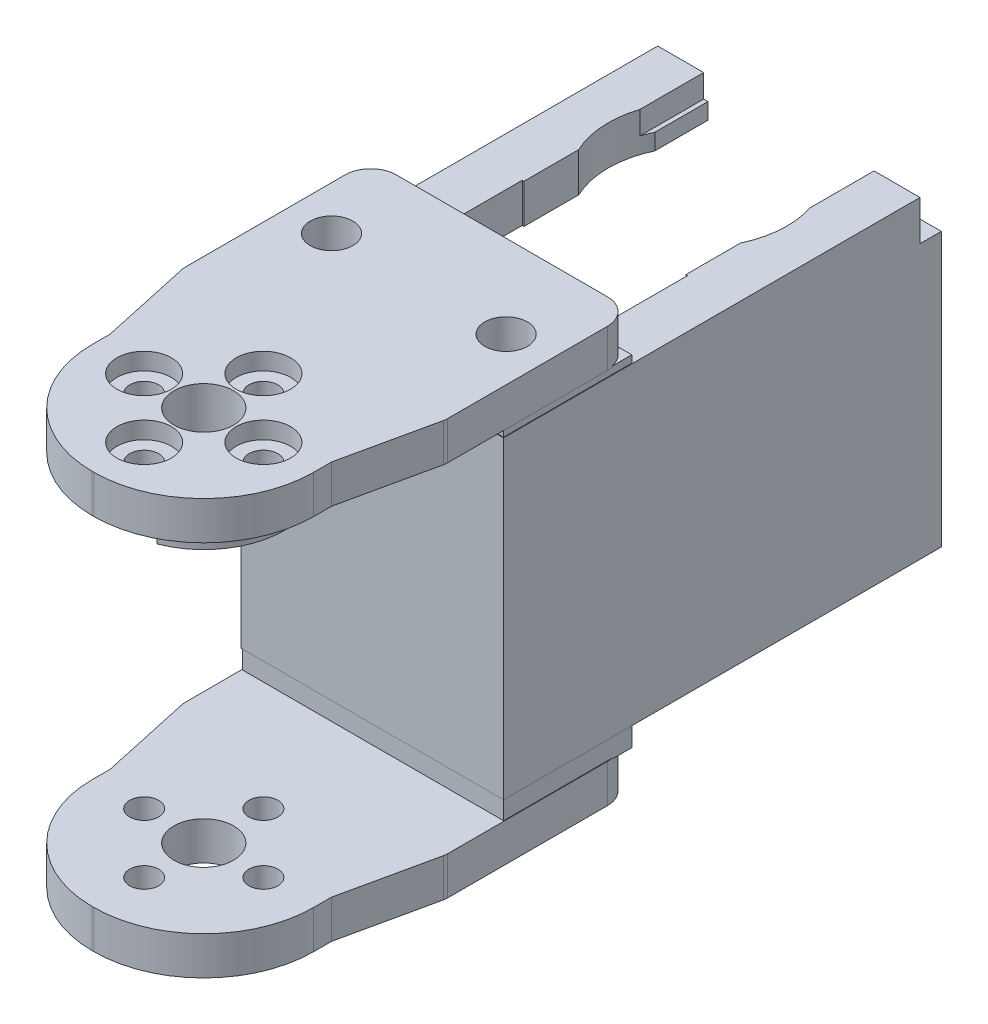
SolidWorks part; units mm, degrees
ref_plane "Front Plane" through (0, 0, 0) normal (0, 0, 1) x (1, 0, 0)
ref_plane "Top Plane" through (0, 0, 0) normal (0, 1, 0) x (1, 0, 0)
ref_plane "Right Plane" through (0, 0, 0) normal (1, 0, 0) x (0, 0, -1)
ref_plane "PY_m23_300" through (0, -23.3, 0) normal (0, 1, 0) x (1, 0, 0)
sketch "S_prism1" plane through (0, -23.3, 0) normal (0, 1, 0) x (1, 0, 0)
  line L0 (-13, 2) -> (-15.354, 12.7893)
  line L1 (-15.4, 13.2156) -> (-15.4, 32)
  line L2 (-12.4, 35) -> (12.4, 35)
  line L3 (15.4, 32) -> (15.4, 13.2156)
  line L4 (15.354, 12.7893) -> (13, 2)
  line L5 (13, 2) -> (13, -0.1)
  line L6 (0.1, -13) -> (-0.1, -13)
  line L7 (-13, -0.1) -> (-13, 2)
  arc A0 (-15.354, 12.7893) -> (-15.4, 13.2156) centre (-13.4076, 13.215) cw
  arc A1 (-15.4, 32) -> (-12.4, 35) centre (-12.3999, 31.9999) cw
  arc A2 (12.4, 35) -> (15.4, 32) centre (12.3999, 31.9999) cw
  arc A3 (15.4, 13.2156) -> (15.354, 12.7893) centre (13.4076, 13.215) cw
  arc A4 (13, -0.1) -> (0.1, -13) centre (0.1001, -0.1001) cw
  arc A5 (-0.1, -13) -> (-13, -0.1) centre (-0.1001, -0.1001) cw
extrude "Boss_1" add sketch "S_prism1" along normal blind 4.5
ref_plane "PY_p17_750" through (0, 17.75, 0) normal (0, 1, 0) x (1, 0, 0)
sketch "S_cyl2" plane through (0, 17.75, 0) normal (0, 1, 0) x (1, 0, 0)
  circle A0 centre (0, 0) radius 9.5
  dimension "D1_S_cyl2" = 19
extrude "Boss_2" add sketch "S_cyl2" along normal blind 3.2
ref_plane "PY_p20_950" through (0, 20.95, 0) normal (0, 1, 0) x (1, 0, 0)
sketch "S_prism3" plane through (0, 20.95, 0) normal (0, 1, 0) x (1, 0, 0)
  line L0 (-13, 2) -> (-15.354, 12.7893)
  line L1 (-15.4, 13.2156) -> (-15.4, 32)
  line L2 (-12.4, 35) -> (12.4, 35)
  line L3 (15.4, 32) -> (15.4, 13.2156)
  line L4 (15.354, 12.7893) -> (13, 2)
  line L5 (13, 2) -> (13, -0.1)
  line L6 (0.1, -13) -> (-0.1, -13)
  line L7 (-13, -0.1) -> (-13, 2)
  arc A0 (-15.354, 12.7893) -> (-15.4, 13.2156) centre (-13.4076, 13.215) cw
  arc A1 (-15.4, 32) -> (-12.4, 35) centre (-12.3999, 31.9999) cw
  arc A2 (12.4, 35) -> (15.4, 32) centre (12.3999, 31.9999) cw
  arc A3 (15.4, 13.2156) -> (15.354, 12.7893) centre (13.4076, 13.215) cw
  arc A4 (13, -0.1) -> (0.1, -13) centre (0.1001, -0.1001) cw
  arc A5 (-0.1, -13) -> (-13, -0.1) centre (-0.1001, -0.1001) cw
extrude "Boss_3" add sketch "S_prism3" along normal blind 4.5
ref_plane "PZ_m22_300" through (0, 0, -22.3) normal (0, 0, 1) x (1, 0, 0)
sketch "S_box4" plane through (0, 0, -22.3) normal (0, 0, 1) x (1, 0, 0)
  line L0 (-15.4, -16.6) -> (15.4, -16.6)
  line L1 (15.4, -16.6) -> (15.4, 20.2)
  line L2 (15.4, 20.2) -> (-15.4, 20.2)
  line L3 (-15.4, 20.2) -> (-15.4, -16.6)
  dimension "P1" = 15.4
  dimension "P2" = 16.6
  dimension "P3" = 15.4
  dimension "P4" = 16.6
  dimension "P5" = 15.4
  dimension "P6" = 20.2
  dimension "P7" = 15.4
  dimension "P8" = 20.2
extrude "Boss_4" add sketch "S_box4" along normal blind 2.5
ref_plane "PZ_m71_200" through (0, 0, -71.2) normal (0, 0, 1) x (1, 0, 0)
sketch "S_box5" plane through (0, 0, -71.2) normal (0, 0, 1) x (1, 0, 0)
  line L0 (12.9, -16.6) -> (15.4, -16.6)
  line L1 (15.4, -16.6) -> (15.4, 20.2)
  line L2 (15.4, 20.2) -> (12.9, 20.2)
  line L3 (12.9, 20.2) -> (12.9, -16.6)
  dimension "P1" = 12.9
  dimension "P2" = 16.6
  dimension "P3" = 15.4
  dimension "P4" = 16.6
  dimension "P5" = 15.4
  dimension "P6" = 20.2
  dimension "P7" = 12.9
  dimension "P8" = 20.2
extrude "Boss_5" add sketch "S_box5" along normal blind 51.4
sketch "S_box6" plane through (0, 0, -71.2) normal (0, 0, 1) x (1, 0, 0)
  line L0 (-15.4, 15.6) -> (15.4, 15.6)
  line L1 (15.4, 15.6) -> (15.4, 20.2)
  line L2 (15.4, 20.2) -> (-15.4, 20.2)
  line L3 (-15.4, 20.2) -> (-15.4, 15.6)
  dimension "P1" = 15.4
  dimension "P2" = 15.6
  dimension "P3" = 15.4
  dimension "P4" = 15.6
  dimension "P5" = 15.4
  dimension "P6" = 20.2
  dimension "P7" = 15.4
  dimension "P8" = 20.2
extrude "Boss_6" add sketch "S_box6" along normal blind 51.4
ref_plane "PZ_m48_000" through (0, 0, -48) normal (0, 0, 1) x (1, 0, 0)
sketch "S_box7" plane through (0, 0, -48) normal (0, 0, 1) x (1, 0, 0)
  line L0 (-15.4, -16.6) -> (-12.9, -16.6)
  line L1 (-12.9, -16.6) -> (-12.9, 20.2)
  line L2 (-12.9, 20.2) -> (-15.4, 20.2)
  line L3 (-15.4, 20.2) -> (-15.4, -16.6)
  dimension "P1" = 15.4
  dimension "P2" = 16.6
  dimension "P3" = 12.9
  dimension "P4" = 16.6
  dimension "P5" = 12.9
  dimension "P6" = 20.2
  dimension "P7" = 15.4
  dimension "P8" = 20.2
extrude "Boss_7" add sketch "S_box7" along normal blind 28.2
ref_plane "PZ_m34_930" through (0, 0, -34.93) normal (0, 0, 1) x (1, 0, 0)
sketch "S_box8" plane through (0, 0, -34.93) normal (0, 0, 1) x (1, 0, 0)
  line L0 (-15.33, -18.9) -> (15.33, -18.9)
  line L1 (15.33, -18.9) -> (15.33, -16.5)
  line L2 (15.33, -16.5) -> (-15.33, -16.5)
  line L3 (-15.33, -16.5) -> (-15.33, -18.9)
  dimension "P1" = 15.33
  dimension "P2" = 18.9
  dimension "P3" = 15.33
  dimension "P4" = 18.9
  dimension "P5" = 15.33
  dimension "P6" = 16.5
  dimension "P7" = 15.33
  dimension "P8" = 16.5
extrude "Boss_8" add sketch "S_box8" along normal blind 15.06
sketch "S_box9" plane through (0, 0, -34.93) normal (0, 0, 1) x (1, 0, 0)
  line L0 (-15.33, 20.1) -> (15.33, 20.1)
  line L1 (15.33, 20.1) -> (15.33, 21.05)
  line L2 (15.33, 21.05) -> (-15.33, 21.05)
  line L3 (-15.33, 21.05) -> (-15.33, 20.1)
  dimension "P1" = 15.33
  dimension "P2" = 20.1
  dimension "P3" = 15.33
  dimension "P4" = 20.1
  dimension "P5" = 15.33
  dimension "P6" = 21.05
  dimension "P7" = 15.33
  dimension "P8" = 21.05
extrude "Boss_9" add sketch "S_box9" along normal blind 15.06
ref_plane "PY_m23_400" through (0, -23.4, 0) normal (0, 1, 0) x (1, 0, 0)
sketch "S_hole10" plane through (0, -23.4, 0) normal (0, 1, 0) x (1, 0, 0)
  circle A0 centre (0, 0) radius 3.5
  dimension "D1_S_hole10" = 7
extrude "Hole_10" cut sketch "S_hole10" along normal blind 4.7
sketch "S_hole11" plane through (0, -23.4, 0) normal (0, 1, 0) x (1, 0, 0)
  circle A0 centre (7, 0) radius 1.7
  dimension "D1_S_hole11" = 3.4
  dimension "P2" = 7
extrude "Hole_11" cut sketch "S_hole11" along normal blind 4.7
sketch "S_hole12" plane through (0, -23.4, 0) normal (0, 1, 0) x (1, 0, 0)
  circle A0 centre (0, -7) radius 1.7
  dimension "D1_S_hole12" = 3.4
  dimension "P2" = 7
extrude "Hole_12" cut sketch "S_hole12" along normal blind 4.7
sketch "S_hole13" plane through (0, -23.4, 0) normal (0, 1, 0) x (1, 0, 0)
  circle A0 centre (-7, 0) radius 1.7
  dimension "D1_S_hole13" = 3.4
  dimension "P2" = 7
extrude "Hole_13" cut sketch "S_hole13" along normal blind 4.7
sketch "S_hole14" plane through (0, -23.4, 0) normal (0, 1, 0) x (1, 0, 0)
  circle A0 centre (0, 7) radius 1.7
  dimension "D1_S_hole14" = 3.4
  dimension "P2" = 7
extrude "Hole_14" cut sketch "S_hole14" along normal blind 4.7
sketch "S_hole15" plane through (0, -23.4, 0) normal (0, 1, 0) x (1, 0, 0)
  circle A0 centre (7, 0) radius 3.2
  dimension "D1_S_hole15" = 6.4
  dimension "P2" = 7
extrude "Hole_15" cut sketch "S_hole15" along normal blind 1.6
sketch "S_hole16" plane through (0, -23.4, 0) normal (0, 1, 0) x (1, 0, 0)
  circle A0 centre (0, -7) radius 3.2
  dimension "D1_S_hole16" = 6.4
  dimension "P2" = 7
extrude "Hole_16" cut sketch "S_hole16" along normal blind 1.6
sketch "S_hole17" plane through (0, -23.4, 0) normal (0, 1, 0) x (1, 0, 0)
  circle A0 centre (-7, 0) radius 3.2
  dimension "D1_S_hole17" = 6.4
  dimension "P2" = 7
extrude "Hole_17" cut sketch "S_hole17" along normal blind 1.6
sketch "S_hole18" plane through (0, -23.4, 0) normal (0, 1, 0) x (1, 0, 0)
  circle A0 centre (0, 7) radius 3.2
  dimension "D1_S_hole18" = 6.4
  dimension "P2" = 7
extrude "Hole_18" cut sketch "S_hole18" along normal blind 1.6
ref_plane "PY_p17_650" through (0, 17.65, 0) normal (0, 1, 0) x (1, 0, 0)
sketch "S_hole19" plane through (0, 17.65, 0) normal (0, 1, 0) x (1, 0, 0)
  circle A0 centre (0, 0) radius 3.5
  dimension "D1_S_hole19" = 7
extrude "Hole_19" cut sketch "S_hole19" along normal blind 7.9
sketch "S_hole20" plane through (0, 17.65, 0) normal (0, 1, 0) x (1, 0, 0)
  circle A0 centre (7, 0) radius 1.7
  dimension "D1_S_hole20" = 3.4
  dimension "P2" = 7
extrude "Hole_20" cut sketch "S_hole20" along normal blind 7.9
sketch "S_hole21" plane through (0, 17.65, 0) normal (0, 1, 0) x (1, 0, 0)
  circle A0 centre (0, -7) radius 1.7
  dimension "D1_S_hole21" = 3.4
  dimension "P2" = 7
extrude "Hole_21" cut sketch "S_hole21" along normal blind 7.9
sketch "S_hole22" plane through (0, 17.65, 0) normal (0, 1, 0) x (1, 0, 0)
  circle A0 centre (-7, 0) radius 1.7
  dimension "D1_S_hole22" = 3.4
  dimension "P2" = 7
extrude "Hole_22" cut sketch "S_hole22" along normal blind 7.9
sketch "S_hole23" plane through (0, 17.65, 0) normal (0, 1, 0) x (1, 0, 0)
  circle A0 centre (0, 7) radius 1.7
  dimension "D1_S_hole23" = 3.4
  dimension "P2" = 7
extrude "Hole_23" cut sketch "S_hole23" along normal blind 7.9
ref_plane "PY_p23_450" through (0, 23.45, 0) normal (0, 1, 0) x (1, 0, 0)
sketch "S_hole24" plane through (0, 23.45, 0) normal (0, 1, 0) x (1, 0, 0)
  circle A0 centre (7, 0) radius 3.2
  dimension "D1_S_hole24" = 6.4
  dimension "P2" = 7
extrude "Hole_24" cut sketch "S_hole24" along normal blind 2.1
sketch "S_hole25" plane through (0, 23.45, 0) normal (0, 1, 0) x (1, 0, 0)
  circle A0 centre (0, -7) radius 3.2
  dimension "D1_S_hole25" = 6.4
  dimension "P2" = 7
extrude "Hole_25" cut sketch "S_hole25" along normal blind 2.1
sketch "S_hole26" plane through (0, 23.45, 0) normal (0, 1, 0) x (1, 0, 0)
  circle A0 centre (-7, 0) radius 3.2
  dimension "D1_S_hole26" = 6.4
  dimension "P2" = 7
extrude "Hole_26" cut sketch "S_hole26" along normal blind 2.1
sketch "S_hole27" plane through (0, 23.45, 0) normal (0, 1, 0) x (1, 0, 0)
  circle A0 centre (0, 7) radius 3.2
  dimension "D1_S_hole27" = 6.4
  dimension "P2" = 7
extrude "Hole_27" cut sketch "S_hole27" along normal blind 2.1
sketch "S_cut28" plane through (0, 0, 0) normal (0, 0, 1) x (1, 0, 0)
  line L0 (-3.4, 17.65) -> (3.4, 17.65)
  line L1 (3.4, 17.65) -> (3.4, 18.65)
  line L2 (3.4, 18.65) -> (-3.4, 18.65)
  line L3 (-3.4, 18.65) -> (-3.4, 17.65)
  dimension "P1" = 3.4
  dimension "P2" = 17.65
  dimension "P3" = 3.4
  dimension "P4" = 17.65
  dimension "P5" = 3.4
  dimension "P6" = 18.65
  dimension "P7" = 3.4
  dimension "P8" = 18.65
extrude "Pocket_28" cut sketch "S_cut28" along normal blind 10
ref_plane "PY_p15_500" through (0, 15.5, 0) normal (0, 1, 0) x (1, 0, 0)
sketch "S_hole29" plane through (0, 15.5, 0) normal (0, 1, 0) x (1, 0, 0)
  circle A0 centre (0, 58) radius 10.5
  dimension "D1_S_hole29" = 21
  dimension "P2" = 58
extrude "Hole_29" cut sketch "S_hole29" along normal blind 4.8
ref_plane "PZ_m47_100" through (0, 0, -47.1) normal (0, 0, 1) x (1, 0, 0)
sketch "S_cut30" plane through (0, 0, -47.1) normal (0, 0, 1) x (1, 0, 0)
  line L0 (-9.7, 15.55) -> (9.7, 15.55)
  line L1 (9.7, 15.55) -> (9.7, 20.3)
  line L2 (9.7, 20.3) -> (-9.7, 20.3)
  line L3 (-9.7, 20.3) -> (-9.7, 15.55)
  dimension "P1" = 9.7
  dimension "P2" = 15.55
  dimension "P3" = 9.7
  dimension "P4" = 15.55
  dimension "P5" = 9.7
  dimension "P6" = 20.3
  dimension "P7" = 9.7
  dimension "P8" = 20.3
extrude "Pocket_30" cut sketch "S_cut30" along normal blind 19.5
ref_plane "PZ_m27_600" through (0, 0, -27.6) normal (0, 0, 1) x (1, 0, 0)
sketch "S_cut31" plane through (0, 0, -27.6) normal (0, 0, 1) x (1, 0, 0)
  line L0 (-8.2, 15.55) -> (8.2, 15.55)
  line L1 (8.2, 15.55) -> (8.2, 20.3)
  line L2 (8.2, 20.3) -> (-8.2, 20.3)
  line L3 (-8.2, 20.3) -> (-8.2, 15.55)
  dimension "P1" = 8.2
  dimension "P2" = 15.55
  dimension "P3" = 8.2
  dimension "P4" = 15.55
  dimension "P5" = 8.2
  dimension "P6" = 20.3
  dimension "P7" = 8.2
  dimension "P8" = 20.3
extrude "Pocket_31" cut sketch "S_cut31" along normal blind 8.3
ref_plane "PZ_m58_000" through (0, 0, -58) normal (0, 0, 1) x (1, 0, 0)
sketch "S_cut32" plane through (0, 0, -58) normal (0, 0, 1) x (1, 0, 0)
  line L0 (-3.5, 15.55) -> (3.5, 15.55)
  line L1 (3.5, 15.55) -> (3.5, 20.3)
  line L2 (3.5, 20.3) -> (-3.5, 20.3)
  line L3 (-3.5, 20.3) -> (-3.5, 15.55)
  dimension "P1" = 3.5
  dimension "P2" = 15.55
  dimension "P3" = 3.5
  dimension "P4" = 15.55
  dimension "P5" = 3.5
  dimension "P6" = 20.3
  dimension "P7" = 3.5
  dimension "P8" = 20.3
extrude "Pocket_32" cut sketch "S_cut32" along normal blind 11
ref_plane "PZ_m71_700" through (0, 0, -71.7) normal (0, 0, 1) x (1, 0, 0)
sketch "S_cut33" plane through (0, 0, -71.7) normal (0, 0, 1) x (1, 0, 0)
  line L0 (-10, 17.5) -> (10, 17.5)
  line L1 (10, 17.5) -> (10, 20.4)
  line L2 (10, 20.4) -> (-10, 20.4)
  line L3 (-10, 20.4) -> (-10, 17.5)
  dimension "P1" = 10
  dimension "P2" = 17.5
  dimension "P3" = 10
  dimension "P4" = 17.5
  dimension "P5" = 10
  dimension "P6" = 20.4
  dimension "P7" = 10
  dimension "P8" = 20.4
extrude "Pocket_33" cut sketch "S_cut33" along normal blind 13.7
sketch "S_hole34" plane through (0, 15.5, 0) normal (0, 1, 0) x (1, 0, 0)
  circle A0 centre (-10.25, 25.25) radius 1.1
  dimension "D1_S_hole34" = 2.2
  dimension "P2" = 10.25
  dimension "P3" = 25.25
extrude "Hole_34" cut sketch "S_hole34" along normal blind 4.8
ref_plane "PY_p18_600" through (0, 18.6, 0) normal (0, 1, 0) x (1, 0, 0)
sketch "S_hole35" plane through (0, 18.6, 0) normal (0, 1, 0) x (1, 0, 0)
  circle A0 centre (-10.25, 25.25) radius 2.3
  dimension "D1_S_hole35" = 4.6
  dimension "P2" = 10.25
  dimension "P3" = 25.25
extrude "Hole_35" cut sketch "S_hole35" along normal blind 1.7
sketch "S_hole36" plane through (0, 15.5, 0) normal (0, 1, 0) x (1, 0, 0)
  circle A0 centre (10.25, 25.25) radius 1.1
  dimension "D1_S_hole36" = 2.2
  dimension "P2" = 10.25
  dimension "P3" = 25.25
extrude "Hole_36" cut sketch "S_hole36" along normal blind 4.8
sketch "S_hole37" plane through (0, 18.6, 0) normal (0, 1, 0) x (1, 0, 0)
  circle A0 centre (10.25, 25.25) radius 2.3
  dimension "D1_S_hole37" = 4.6
  dimension "P2" = 10.25
  dimension "P3" = 25.25
extrude "Hole_37" cut sketch "S_hole37" along normal blind 1.7
ref_plane "PZ_m71_300" through (0, 0, -71.3) normal (0, 0, 1) x (1, 0, 0)
sketch "S_cut38" plane through (0, 0, -71.3) normal (0, 0, 1) x (1, 0, 0)
  line L0 (-15.5, 15.5) -> (15.5, 15.5)
  line L1 (15.5, 15.5) -> (15.5, 20.3)
  line L2 (15.5, 20.3) -> (-15.5, 20.3)
  line L3 (-15.5, 20.3) -> (-15.5, 15.5)
  dimension "P1" = 15.5
  dimension "P2" = 15.5
  dimension "P3" = 15.5
  dimension "P4" = 15.5
  dimension "P5" = 15.5
  dimension "P6" = 20.3
  dimension "P7" = 15.5
  dimension "P8" = 20.3
extrude "Pocket_38" cut sketch "S_cut38" along normal blind 2.6
ref_plane "PZ_m68_800" through (0, 0, -68.8) normal (0, 0, 1) x (1, 0, 0)
sketch "S_cut39" plane through (0, 0, -68.8) normal (0, 0, 1) x (1, 0, 0)
  line L0 (-9.5, 15.55) -> (9.5, 15.55)
  line L1 (9.5, 15.55) -> (9.5, 20.3)
  line L2 (9.5, 20.3) -> (-9.5, 20.3)
  line L3 (-9.5, 20.3) -> (-9.5, 15.55)
  dimension "P1" = 9.5
  dimension "P2" = 15.55
  dimension "P3" = 9.5
  dimension "P4" = 15.55
  dimension "P5" = 9.5
  dimension "P6" = 20.3
  dimension "P7" = 9.5
  dimension "P8" = 20.3
extrude "Pocket_39" cut sketch "S_cut39" along normal blind 22.2
ref_plane "PZ_m49_900" through (0, 0, -49.9) normal (0, 0, 1) x (1, 0, 0)
sketch "S_cut40" plane through (0, 0, -49.9) normal (0, 0, 1) x (1, 0, 0)
  line L0 (-7.5, -17.75) -> (7.5, -17.75)
  line L1 (7.5, -17.75) -> (7.5, -16.2)
  line L2 (7.5, -16.2) -> (-7.5, -16.2)
  line L3 (-7.5, -16.2) -> (-7.5, -17.75)
  dimension "P1" = 7.5
  dimension "P2" = 17.75
  dimension "P3" = 7.5
  dimension "P4" = 17.75
  dimension "P5" = 7.5
  dimension "P6" = 16.2
  dimension "P7" = 7.5
  dimension "P8" = 16.2
extrude "Pocket_40" cut sketch "S_cut40" along normal blind 27.4
ref_plane "PY_p20_250" through (0, 20.25, 0) normal (0, 1, 0) x (1, 0, 0)
sketch "S_hole41" plane through (0, 20.25, 0) normal (0, 1, 0) x (1, 0, 0)
  circle A0 centre (-10.25, 25.25) radius 2.5
  dimension "D1_S_hole41" = 5
  dimension "P2" = 10.25
  dimension "P3" = 25.25
extrude "Hole_41" cut sketch "S_hole41" along normal blind 5.3
sketch "S_hole42" plane through (0, 20.25, 0) normal (0, 1, 0) x (1, 0, 0)
  circle A0 centre (10.25, 25.25) radius 2.5
  dimension "D1_S_hole42" = 5
  dimension "P2" = 10.25
  dimension "P3" = 25.25
extrude "Hole_42" cut sketch "S_hole42" along normal blind 5.3
equation "\"plate_t\" = 3"
equation "\"clearance\" = 0.5"
